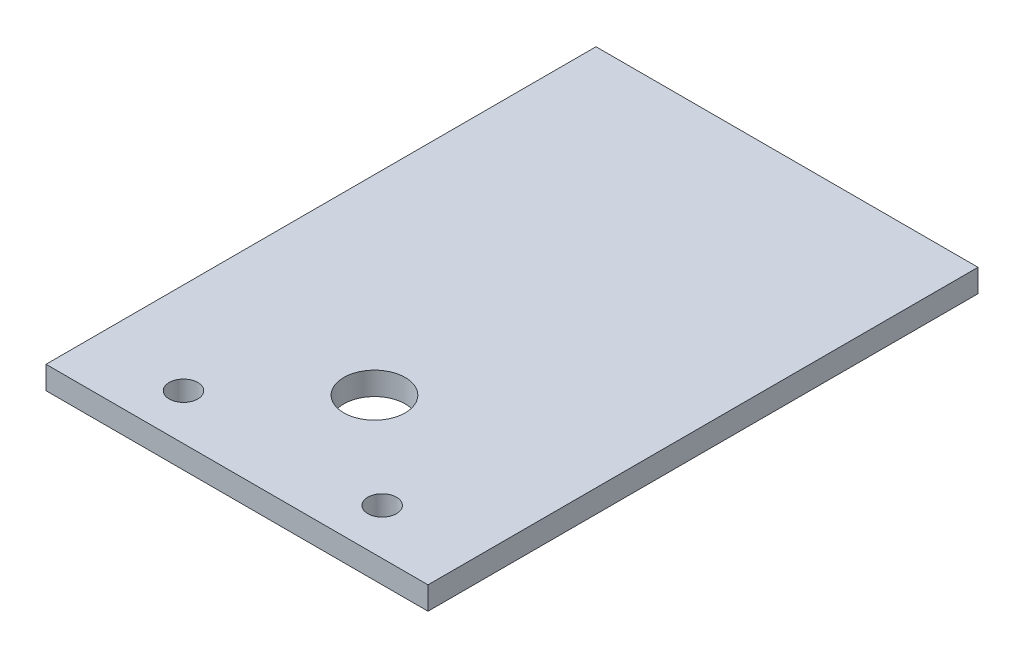
SolidWorks part; units mm, degrees
material "6061 Alloy"
ref_plane "Front Plane" through (0, 0, 0) normal (0, 0, 1) x (1, 0, 0)
ref_plane "Top Plane" through (0, 0, 0) normal (0, 1, 0) x (1, 0, 0)
ref_plane "Right Plane" through (0, 0, 0) normal (1, 0, 0) x (0, 0, -1)
sketch "Sketch1" plane through (0, 0, 0) normal (0, 1, 0) x (1, 0, 0)
  line L1 (-52.925, 76.2) -> (52.925, 76.2)
  line L2 (-52.925, 76.2) -> (-52.925, -76.2)
  line L3 (-52.925, -76.2) -> (52.925, -76.2)
  line L4 (52.925, 76.2) -> (52.925, -76.2)
  line L5 (-52.925, 76.2) -> (52.925, -76.2) construction
  line L6 (-52.925, -76.2) -> (52.925, 76.2) construction
  point P0 (0, 0)
  dimension "D1" = 152.4
  dimension "D2" = 105.85
extrude "Boss-Extrude1" add sketch "Sketch1" along normal blind 6.35
sketch "Sketch2" plane through (0, 6.35, 0) normal (0, 1, 0) x (1, 0, 0)
  line L0 (0, 0) -> (0, -11.2478) construction
  line L1 (0, 0) -> (-15.1024, 0) construction
  line L2 (-52.925, -76.2) -> (52.925, -76.2) construction
  line L3 (-52.925, 76.2) -> (-52.925, -76.2) construction
  circle A0 centre (-27.525, -63.5) radius 3.9688
  circle A1 centre (27.525, -63.5) radius 3.9688
  circle A2 centre (0, -38.1) radius 8.5
  dimension "D1" = 12.7
  dimension "D2" = 25.4
  dimension "D3" = 17
  dimension "D4" = 38.1
extrude "Cut-Extrude1" cut sketch "Sketch2" against normal up to next
